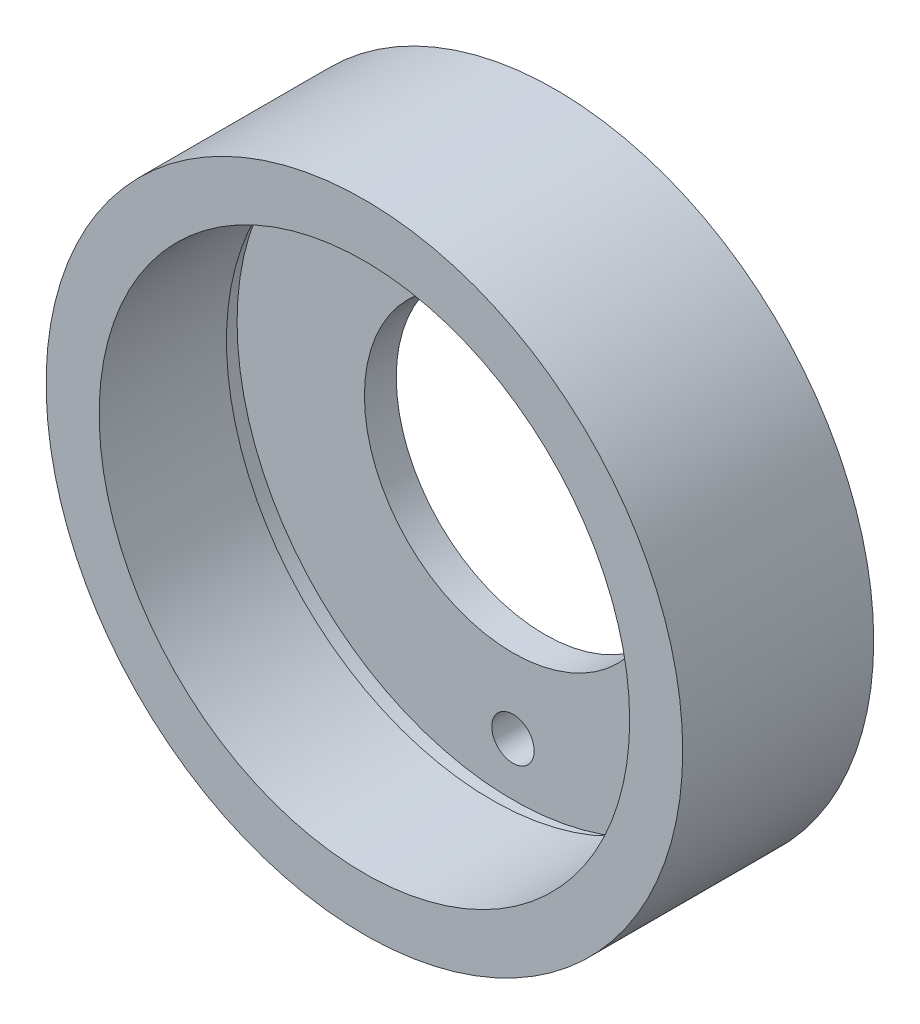
SolidWorks part; units mm, degrees
material "Alliage de zinc AC41A, brut"
ref_plane "Plan de face" through (0, 0, 0) normal (0, 0, 1) x (1, 0, 0)
ref_plane "Plan de dessus" through (0, 0, 0) normal (0, 1, 0) x (1, 0, 0)
ref_plane "Plan de droite" through (0, 0, 0) normal (1, 0, 0) x (0, 0, -1)
sketch "Esquisse1" plane through (0, 0, 0) normal (0, 0, 1) x (1, 0, 0)
  circle A0 centre (0, 0) radius 15
  dimension "D1" = 30
extrude "Boss.-Extru.1" add sketch "Esquisse1" along normal blind 2
sketch "Esquisse2" plane through (0, 0, 2) normal (0, 0, 1) x (1, 0, 0)
  circle A0 centre (0, 0) radius 15
  circle A1 centre (0, 0) radius 13
  dimension "D1" = 30
  dimension "D2" = 26
extrude "Boss.-Extru.2" add sketch "Esquisse2" along normal blind 1
sketch "Esquisse3" plane through (0, 0, 3) normal (0, 0, 1) x (1, 0, 0)
  circle A0 centre (0, 0) radius 12.5
  circle A1 centre (0, 0) radius 15
  dimension "D1" = 25
  dimension "D2" = 30
extrude "Boss.-Extru.3" add sketch "Esquisse3" along normal blind 6
cosmetic thread "Représentation de filetage1" parameters "D2"=26
sketch "Esquisse5" plane through (0, 0, 0) normal (0, 0, -1) x (-1, 0, 0)
  circle A1 centre (0, 0) radius 8.5
  dimension "D1" = 17
extrude "Enlèv. mat.-Extru.1" cut sketch "Esquisse5" against normal blind 0.5
sketch "Esquisse6" plane through (0, 0, 0.5) normal (0, 0, -1) x (-1, 0, 0)
  circle A0 centre (0, 0) radius 7
  dimension "D1" = 14
extrude "Enlèv. mat.-Extru.2" cut sketch "Esquisse6" against normal blind 1.5
sketch "Esquisse9" plane through (0, 0, 0) normal (0, 0, -1) x (-1, 0, 0)
  line L0 (0, 0) -> (0, 10.5) construction
  line L2 (0, 0) -> (0, -10.5) construction
  point P2 (0, 10.5)
  point P13 (0, -10.5)
  point P17 (0, 10.5)
  point P18 (0, -10.5)
  dimension "D2" = 2
  dimension "D1" = 10.5
hole_wizard "Diamètre du perçage Ø2.0 (2)1" positions "Esquisse9" profile "Esquisse8" hole size "Ø2.0" standard "ISO" end condition through all
sketch "Esquisse8" plane through (0, -10.5, 0) normal (1, 0, 0) x (0, 1, 0)
  line L0 (0, 0) -> (0, 9)
  line L1 (0, 9) -> (1, 9)
  line L2 (1, 9) -> (1, 0.025)
  line L3 (1, 0.025) -> (1.025, 0)
  line L5 (1.025, 0) -> (0, 0)
  line L6 (-1, 0.025) -> (-1.025, 0) construction
  line L11 (0, -6.35) -> (0, 107.95) construction
  dimension "Diamètre du perçage jusqu'au prochain" = 2
  dimension "Profondeur du perçage jusqu'au prochain" = 9
  dimension "Diamètre du fraisage entrant" = 2.05
  dimension "Angle du fraisage entrant" = 90
